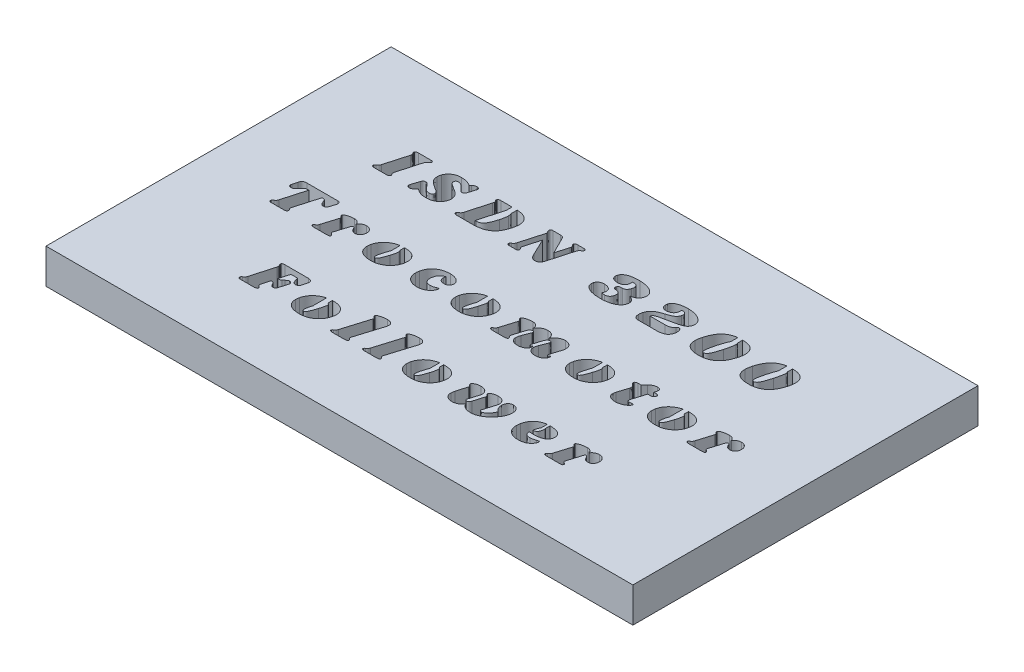
SolidWorks part; units mm, degrees
ref_plane "前视基准面" through (0, 0, 0) normal (0, 0, 1) x (1, 0, 0)
ref_plane "上视基准面" through (0, 0, 0) normal (0, 1, 0) x (1, 0, 0)
ref_plane "右视基准面" through (0, 0, 0) normal (1, 0, 0) x (0, 0, -1)
sketch "Sketch2" plane through (0, 0, 0) normal (0, 1, 0) x (1, 0, 0)
  line L1 (-84.2031, -49.5174) -> (84.2031, -49.5174)
  line L2 (-84.2031, -49.5174) -> (-84.2031, 49.5174)
  line L3 (-84.2031, 49.5174) -> (84.2031, 49.5174)
  line L4 (84.2031, -49.5174) -> (84.2031, 49.5174)
  line L5 (-84.2031, -49.5174) -> (84.2031, 49.5174) construction
  line L6 (-84.2031, 49.5174) -> (84.2031, -49.5174) construction
  point P0 (0, 0)
  dimension "D1" = 168.4063
  dimension "D2" = 99.0348
extrude "Boss-Extrude1" add sketch "Sketch2" along normal blind 10
sketch "Sketch1" plane through (0, 10, 0) normal (0, 1, 0) x (1, 0, 0)
  line L0 (-75, 17.0642) -> (75, 17.0642) construction
  line L5 (-75, 44.2771) -> (75, -44.2771) construction
  line L6 (-75, -44.2771) -> (75, 44.2771) construction
  text T0 "ISDN 3200\r\nTrocomotor\r\nFollower" font "Shrikhand" height 10
  point P0 (0, 0)
  dimension "D1" = 150
extrude "Cut-Extrude1" cut sketch "Sketch1" against normal through all
sketch "Sketch3" plane through (0, 10, 0) normal (0, 1, 0) x (1, 0, 0)
  line L1 (32.0062, -20.6674) -> (32.78, -20.6674)
  line L2 (32.0062, -20.6674) -> (32.0062, -24.1127)
  line L3 (32.0062, -24.1127) -> (32.78, -24.1127)
  line L4 (32.78, -20.6674) -> (32.78, -24.1127)
  line L5 (24.5419, 2.3608) -> (25.8525, 2.3608)
  line L6 (24.5419, 2.3608) -> (24.5419, -1.5304)
  line L7 (24.5419, -1.5304) -> (25.8525, -1.5304)
  line L8 (25.8525, 2.3608) -> (25.8525, -1.5304)
  line L9 (47.7084, 2.9436) -> (49.1058, 2.9436)
  line L10 (47.7084, 2.9436) -> (47.7084, -2.4696)
  line L11 (47.7084, -2.4696) -> (49.1058, -2.4696)
  line L12 (49.1058, 2.9436) -> (49.1058, -2.4696)
  line L13 (37.7958, 28.0316) -> (39.1116, 28.0316)
  line L14 (37.7958, 28.0316) -> (37.7958, 23.8105)
  line L15 (37.7958, 23.8105) -> (39.1116, 23.8105)
  line L16 (39.1116, 28.0316) -> (39.1116, 23.8105)
  line L17 (51.8812, 28.8904) -> (53.4466, 28.8904)
  line L18 (51.8812, 28.8904) -> (51.8812, 23.8105)
  line L19 (51.8812, 23.8105) -> (53.4466, 23.8105)
  line L20 (53.4466, 28.8904) -> (53.4466, 23.8105)
  line L21 (-33.5337, 2.9436) -> (-32.3597, 2.9436)
  line L22 (-33.5337, 2.9436) -> (-33.5337, -1.0425)
  line L23 (-33.5337, -1.0425) -> (-32.3597, -1.0425)
  line L24 (-32.3597, 2.9436) -> (-32.3597, -1.0425)
  line L25 (-8.4018, 2.7219) -> (-6.9887, 2.7219)
  line L26 (-8.4018, 2.7219) -> (-8.4018, -1.5304)
  line L27 (-8.4018, -1.5304) -> (-6.9887, -1.5304)
  line L28 (-6.9887, 2.7219) -> (-6.9887, -1.5304)
  line L29 (-31.0755, -20.4762) -> (-29.6046, -20.4762)
  line L30 (-31.0755, -20.4762) -> (-31.0755, -25.9379)
  line L31 (-31.0755, -25.9379) -> (-29.6046, -25.9379)
  line L32 (-29.6046, -20.4762) -> (-29.6046, -25.9379)
  line L33 (1.2676, -20.4762) -> (2.3362, -20.4762)
  line L34 (1.2676, -20.4762) -> (1.2676, -25.7474)
  line L35 (1.2676, -25.7474) -> (2.3362, -25.7474)
  line L36 (2.3362, -20.4762) -> (2.3362, -25.7474)
  line L37 (-27.0409, 29.429) -> (-25.5542, 29.429)
  line L38 (-27.0409, 29.429) -> (-27.0409, 22.8499)
  line L39 (-27.0409, 22.8499) -> (-25.5542, 22.8499)
  line L40 (-25.5542, 29.429) -> (-25.5542, 22.8499)
  spline S0 degree 3 poles (31.5533, -25.4122) (31.6042, -25.4108) (31.7038, -25.4081) (31.8484, -25.3784) (31.9842, -25.3327) (32.1118, -25.2699) (32.2276, -25.1861) (32.3332, -25.0836) (32.431, -24.9646) (32.5458, -24.78) (32.6636, -24.528) (32.7673, -24.2072) (32.8246, -23.8682) (32.8287, -23.6375) (32.8308, -23.5199) knots 0 0 0 0 0.059844 0.117259 0.173131 0.228479 0.284142 0.340887 0.401541 0.465236 0.596571 0.728297 0.8616 1 1 1 1 construction
  spline S1 degree 3 poles (25.5803, -2.4696) (25.6167, -2.3524) (25.6866, -2.127) (25.7845, -1.8014) (25.8605, -1.4982) (25.9304, -1.2218) (25.9796, -0.9684) (26.0174, -0.7411) (26.0411, -0.5381) (26.0439, -0.4109) (26.0452, -0.3515) knots 0 0 0 0 0.16931 0.325417 0.468808 0.600329 0.718426 0.824648 0.918057 1 1 1 1 construction
  spline S2 degree 3 poles (47.6046, -5.2331) (47.6308, -5.2334) (47.6846, -5.2343) (47.7665, -5.2135) (47.8482, -5.1722) (47.931, -5.1136) (48.0106, -5.0326) (48.0942, -4.9373) (48.1751, -4.8207) (48.263, -4.6862) (48.349, -4.5223) (48.4427, -4.3292) (48.5397, -4.1017) (48.6443, -3.8413) (48.7519, -3.5461) (48.8647, -3.217) (48.9839, -2.8548) (49.0641, -2.6015) (49.1058, -2.4696) knots 0 0 0 0 0.02391 0.049192 0.07651 0.107459 0.141733 0.180332 0.223629 0.271698 0.327547 0.393171 0.468405 0.554213 0.650415 0.756446 0.873179 1 1 1 1 construction
  spline S3 degree 3 poles (49.1058, -2.4696) (49.1422, -2.3524) (49.2121, -2.127) (49.31, -1.8014) (49.386, -1.4982) (49.4559, -1.2218) (49.5051, -0.9684) (49.5429, -0.7411) (49.5666, -0.5381) (49.5694, -0.4109) (49.5707, -0.3515) knots 0 0 0 0 0.16931 0.325417 0.468808 0.600329 0.718426 0.824648 0.918057 1 1 1 1 construction
  spline S4 degree 3 poles (38.6796, 22.0349) (38.7256, 22.2064) (38.8138, 22.5352) (38.9342, 23.0085) (39.0334, 23.4405) (39.1173, 23.829) (39.181, 24.1761) (39.2263, 24.4811) (39.258, 24.7441) (39.2621, 24.9054) (39.264, 24.9787) knots 0 0 0 0 0.177157 0.339578 0.487129 0.619322 0.736081 0.839064 0.926979 1 1 1 1 construction
  spline S5 degree 3 poles (53.0146, 22.0349) (53.0606, 22.2064) (53.1487, 22.5352) (53.2692, 23.0085) (53.3684, 23.4405) (53.4523, 23.829) (53.516, 24.1761) (53.5613, 24.4811) (53.593, 24.7441) (53.5971, 24.9054) (53.599, 24.9787) knots 0 0 0 0 0.177157 0.339578 0.487129 0.619322 0.736081 0.839064 0.926979 1 1 1 1 construction
  spline S6 degree 3 poles (-7.2609, -2.4696) (-7.2245, -2.3524) (-7.1546, -2.127) (-7.0567, -1.8014) (-6.9807, -1.4982) (-6.9108, -1.2218) (-6.8616, -0.9684) (-6.8238, -0.7411) (-6.8001, -0.5381) (-6.7973, -0.4109) (-6.796, -0.3515) knots 0 0 0 0 0.16931 0.325417 0.468808 0.600329 0.718426 0.824648 0.918057 1 1 1 1 construction
  spline S7 degree 3 poles (-29.6046, -25.9379) (-29.5682, -25.8207) (-29.4983, -25.5953) (-29.4004, -25.2697) (-29.3244, -24.9665) (-29.2545, -24.6901) (-29.2053, -24.4367) (-29.1675, -24.2094) (-29.1438, -24.0064) (-29.141, -23.8792) (-29.1397, -23.8197) knots 0 0 0 0 0.16931 0.325417 0.468808 0.600329 0.718426 0.824648 0.918057 1 1 1 1 construction
  spline S8 degree 3 poles (2.2772, -25.9379) (2.3136, -25.8207) (2.3835, -25.5953) (2.4814, -25.2697) (2.5574, -24.9665) (2.6274, -24.6901) (2.6765, -24.4367) (2.7143, -24.2094) (2.738, -24.0064) (2.7408, -23.8792) (2.7421, -23.8197) knots 0 0 0 0 0.16931 0.325417 0.468808 0.600329 0.718426 0.824648 0.918057 1 1 1 1 construction
  spline S9 degree 3 poles (-25.7436, 22.0958) (-25.7126, 22.21) (-25.6525, 22.4314) (-25.5749, 22.7562) (-25.5065, 23.0616) (-25.4529, 23.3487) (-25.4081, 23.6165) (-25.3776, 23.8658) (-25.3595, 24.0971) (-25.3563, 24.245) (-25.3548, 24.316) knots 0 0 0 0 0.157154 0.304503 0.443278 0.57242 0.692208 0.803569 0.905752 1 1 1 1 construction
extrude "Boss-Extrude2" add sketch "Sketch3" against normal blind 10
